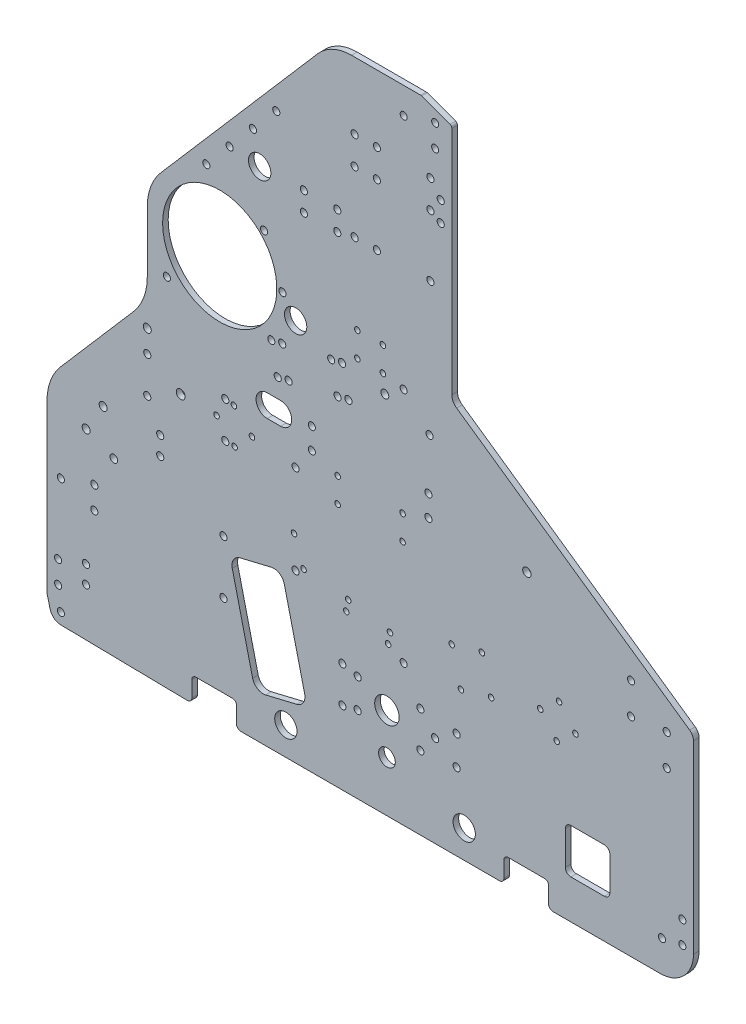
SolidWorks part; units mm, degrees
ref_plane "Front Plane" through (0, 0, 0) normal (0, 0, 1) x (1, 0, 0)
ref_plane "Top Plane" through (0, 0, 0) normal (0, 1, 0) x (1, 0, 0)
ref_plane "Right Plane" through (0, 0, 0) normal (1, 0, 0) x (0, 0, -1)
sketch "Sketch1" plane through (0, 0, 0) normal (0, 0, 1) x (1, 0, 0)
  line L0 (82.55, -20.32) -> (82.55, -6.35)
  line L2 (0, 0) -> (0, 157.48)
  line L4 (368.3, -20.32) -> (368.3, 106.68)
  line L5 (82.55, -6.35) -> (107.95, -6.35)
  line L6 (107.95, -6.35) -> (107.95, -20.32)
  line L7 (107.95, -20.32) -> (260.35, -20.32)
  line L8 (260.35, -20.32) -> (260.35, -6.35)
  line L9 (260.35, -6.35) -> (285.75, -6.35)
  line L10 (285.75, -6.35) -> (285.75, -20.32)
  line L11 (285.75, -20.32) -> (368.3, -20.32)
  line L12 (361.95, 12.7) -> (368.3, 12.7) construction
  line L13 (0, 0) -> (6.35, 0) construction
  line L14 (0.1896, -7.8901) -> (1.7771, -14.2401)
  line L15 (7.8295, -19.0491) -> (82.55, -20.32)
  line L16 (0, 0) -> (0, -6.35)
  line L17 (76.2, 128.905) -> (79.375, 128.905) construction
  line L18 (57.15, 118.5863) -> (101.6, 118.5862) construction
  line L19 (57.15, 118.5863) -> (57.15, 139.2238) construction
  line L20 (101.6, 118.5862) -> (101.6, 139.2237) construction
  line L21 (57.15, 139.2238) -> (101.6, 139.2237) construction
  line L22 (57.15, 118.5863) -> (101.6, 139.2237) construction
  line L23 (101.6, 118.5862) -> (57.15, 139.2238) construction
  line L24 (101.6, 139.2237) -> (125.4682, 147.9111) construction
  line L25 (203.2, 59.805) -> (203.2, 194.805) construction
  line L26 (203.2, 194.805) -> (203.2, 329.805) construction
  line L27 (355.6, 332.105) -> (330.2, 332.105) construction
  line L28 (330.2, 332.105) -> (330.2, 217.805) construction
  line L29 (330.2, 217.805) -> (355.6, 217.805) construction
  line L30 (355.6, 217.805) -> (355.6, 332.105) construction
  line L31 (203.2, 344.805) -> (203.2, 194.805) construction
  line L32 (50.8, 332.105) -> (76.2, 332.105) construction
  line L33 (76.2, 332.105) -> (76.2, 217.805) construction
  line L34 (50.8, 217.805) -> (50.8, 332.105) construction
  line L35 (76.2, 217.805) -> (50.8, 217.805) construction
  line L36 (213.2, 344.805) -> (230.6638, 338.455)
  line L37 (203.2, 344.805) -> (161.925, 344.805)
  line L38 (203.2, 344.805) -> (213.2, 344.805)
  line L39 (348.5362, 344.805) -> (413.4623, 344.805)
  line L40 (348.5362, 344.805) -> (230.6638, 344.805) construction
  line L42 (161.925, 344.805) -> (0, 157.48)
  line L44 (230.6638, 338.455) -> (230.6638, 202.565)
  line L45 (230.6638, 202.565) -> (368.3, 106.68)
  line L46 (213.2, 344.805) -> (-141.0713, 344.805) construction
  line L47 (350.3395, -2.3595) -> (368.3, -20.32) construction
  line L48 (125.4682, 147.9111) -> (133.0882, 147.9111) construction
  line L49 (125.4682, 154.2611) -> (133.0882, 154.2611)
  line L50 (125.4682, 141.5611) -> (133.0882, 141.5611)
  circle A0 centre (6.35, 0) radius 2.032
  circle A1 centre (6.35, 12.7) radius 2.032
  circle A2 centre (361.95, 0) radius 2.032
  circle A3 centre (361.95, 12.7) radius 2.032
  arc A5 (1.7771, -14.2401) -> (7.8295, -19.0491) centre (7.9375, -12.7) ccw
  circle A6 centre (7.9375, -12.7) radius 2.032
  arc A7 (0, -6.35) -> (0.1896, -7.8901) centre (6.35, -6.35) ccw
  circle A8 centre (38.1, 78.105) radius 2.032
  circle A9 centre (76.2, 128.905) radius 2.54
  circle A10 centre (101.6, 118.5862) radius 2.032
  circle A11 centre (101.6, 139.2237) radius 2.032
  circle A12 centre (57.15, 139.2238) radius 2.032
  circle A13 centre (57.15, 118.5863) radius 2.032
  circle A15 centre (203.2, 59.805) radius 2
  circle A16 centre (203.2, 194.805) radius 2
  circle A17 centre (203.2, 329.805) radius 2
  circle A18 centre (63.5, 313.055) radius 2.032
  circle A20 centre (355.6, 332.105) radius 2.032
  circle A21 centre (330.2, 332.105) radius 2.032
  circle A22 centre (355.6, 217.805) radius 2.032
  circle A23 centre (330.2, 217.805) radius 2.032
  circle A24 centre (50.8, 332.105) radius 2.032
  circle A25 centre (76.2, 332.105) radius 2.032
  circle A26 centre (50.8, 217.805) radius 2.032
  circle A27 centre (76.2, 217.805) radius 2.032
  circle A28 centre (221.1381, 335.28) radius 2
  circle A29 centre (224.3138, 298.831) radius 2.032
  circle A30 centre (353.06, 100.7351) radius 2.032
  circle A31 centre (332.74, 115.9751) radius 2.032
  circle A32 centre (332.74, 98.1951) radius 2.032
  circle A33 centre (353.06, 82.9551) radius 2.032
  circle A34 centre (117.3562, 280.4276) radius 2.032
  circle A35 centre (104.0678, 265.0548) radius 2.032
  circle A36 centre (90.7795, 249.682) radius 2.032
  circle A38 centre (130.6445, 295.8004) radius 2.032
  circle A39 centre (68.326, 182.9237) radius 2.032
  circle A40 centre (224.3138, 287.401) radius 2.032
  circle A41 centre (125.4682, 147.9111) radius 6.35
  circle A42 centre (221.1381, 322.58) radius 2
  circle A43 centre (350.3395, -2.3595) radius 2.032
  arc A44 (125.4682, 154.2611) -> (125.4682, 141.5611) centre (125.4682, 147.9111) ccw
  arc A45 (133.0882, 141.5611) -> (133.0882, 154.2611) centre (133.0882, 147.9111) ccw
  point P82 (203.2, 344.805)
  point P90 (368.3, 62.484)
  point P107 (129.2782, 147.9111)
  dimension "D6" = 4.064
  dimension "D10" = 6.35
  dimension "D11" = 4.064
  dimension "D17" = 38.1
  dimension "D27" = 4
  dimension "D31" = 4.064
  dimension "D32" = 41.275
  dimension "D36" = 4.064
  dimension "D47" = 39.624
  dimension "D48" = 4.064
  dimension "D25" = 5.08
  dimension "D26" = 4.064
  dimension "D52" = 4.064
  dimension "D65" = 4.064
  dimension "D69" = 4.064
  dimension "D72" = 12.7
  dimension "D77" = 6.35
  dimension "D2" = 127
  dimension "D3" = 13.97
  dimension "D4" = 25.4
  dimension "D5" = 152.4
  dimension "D7" = 12.7
  dimension "D8" = 6.35
  dimension "D9" = 20.32
  dimension "D12" = 12.7
  dimension "D13" = 1.5875
  dimension "D14" = 82.55
  dimension "D15" = 368.3
  dimension "D16" = 6.35
  dimension "D18" = 98.425
  dimension "D19" = 38.1
  dimension "D20" = 50.8
  dimension "D21" = 3.175
  dimension "D22" = 270
  dimension "D23" = 20.6375
  dimension "D24" = 44.45
  dimension "D28" = 135
  dimension "D29" = 12.7
  dimension "D30" = 15
  dimension "D33" = 63.5
  dimension "D34" = 27.4638
  dimension "D35" = 12.7
  dimension "D37" = 114.3
  dimension "D38" = 25.4
  dimension "D39" = 12.7
  dimension "D40" = 157.48
  dimension "D41" = 142.24
  dimension "D42" = 365.125
  dimension "D43" = 10
  dimension "D44" = 6.35
  dimension "D45" = 31.75
  dimension "D46" = 3.175
  dimension "D49" = 6.35
  dimension "D50" = 203.2
  dimension "D51" = 15.24
  dimension "D53" = 17.78
  dimension "D54" = 17.78
  dimension "D55" = 20.32
  dimension "D56" = 15.24
  dimension "D57" = 92.202
  dimension "D58" = 8.382
  dimension "D59" = 20.32
  dimension "D60" = 20.32
  dimension "D61" = 8.382
  dimension "D62" = 20.32
  dimension "D63" = 8.382
  dimension "D64" = 8.382
  dimension "D66" = 35.052
  dimension "D67" = 68.326
  dimension "D68" = 11.43
  dimension "D70" = 25.4
  dimension "D71" = 110
  dimension "D73" = 17.9381
  dimension "D74" = 12.7
  dimension "D75" = 45
  dimension "D76" = 25.4
  dimension "D79" = 7.62
extrude "Boss-Extrude1" add sketch "Sketch1" along normal blind 3.175 contours L16 A7 L14 A5 L15 L2 A0 A1 A6 region at (171.4194, 119.4541, 0)
fillet "Fillet1" radius 2.286 4 edges at (285.75, -6.35, 1.5875) (107.95, -6.35, 1.5875) (260.35, -6.35, 1.5875) (82.55, -6.35, 1.5875)
fillet "Fillet2" radius 6.35 1 edges at (230.6638, 202.565, 1.5875)
sketch "Sketch2" plane through (0, 0, 0) normal (0, 0, -1) x (-1, 0, 0)
  circle A0 centre (-100.5528, 71.086) radius 2.032 construction
  circle A1 centre (-100.5528, 40.606) radius 2.032 construction
  circle A2 centre (-22.225, 18.2025) radius 2.032 construction
  circle A3 centre (-22.225, 8.0425) radius 2.032 construction
  circle A4 centre (-100.5528, 71.086) radius 2.032
  circle A5 centre (-100.5528, 40.606) radius 2.032
  circle A6 centre (-22.225, 18.2025) radius 2.032
  circle A7 centre (-22.225, 8.0425) radius 2.032
extrude "Cut-Extrude1" cut sketch "Sketch2" against normal through all
fillet "Fillet3" radius 1.5875 2 edges at (230.6638, 338.455, 1.5875) (213.2, 344.805, 1.5875)
sketch "Sketch3" plane through (0, 0, 3.175) normal (0, 0, 1) x (1, 0, 0)
  line L0 (132.9524, 63.2646) -> (132.7215, 64.2281) construction
  line L1 (128.3814, 66.8897) -> (110.6828, 62.6472) construction
  line L2 (114.5132, 58.4237) -> (126.8822, 61.3887) construction
  line L3 (108.0212, 58.3071) -> (108.2522, 57.3436) construction
  line L4 (131.2006, 57.703) -> (140.0164, 20.9265) construction
  line L5 (144.0993, 16.7636) -> (132.9524, 63.2646) construction
  line L6 (108.2522, 57.3436) -> (119.3991, 10.8426) construction
  line L7 (121.1509, 16.4042) -> (112.3351, 53.1807) construction
  line L8 (119.3991, 10.8426) -> (119.6301, 9.8791) construction
  line L9 (144.3303, 15.8001) -> (144.0993, 16.7636) construction
  line L10 (137.8383, 15.6835) -> (125.4694, 12.7185) construction
  line L11 (123.9701, 7.2175) -> (141.6687, 11.4601) construction
  line L12 (132.9524, 63.2646) -> (132.7215, 64.2281)
  line L13 (128.3814, 66.8897) -> (110.6828, 62.6472)
  line L14 (114.5132, 58.4237) -> (126.8822, 61.3887)
  line L15 (108.0212, 58.3071) -> (108.2522, 57.3436)
  line L16 (131.2006, 57.703) -> (140.0164, 20.9265)
  line L17 (144.0993, 16.7636) -> (132.9524, 63.2646)
  line L18 (108.2522, 57.3436) -> (119.3991, 10.8426)
  line L19 (121.1509, 16.4042) -> (112.3351, 53.1807)
  line L20 (119.3991, 10.8426) -> (119.6301, 9.8791)
  line L21 (144.3303, 15.8001) -> (144.0993, 16.7636)
  line L22 (137.8383, 15.6835) -> (125.4694, 12.7185)
  line L23 (123.9701, 7.2175) -> (141.6687, 11.4601)
  line L24 (127.7894, 69.3598) -> (110.0908, 65.1172)
  line L25 (105.5512, 57.715) -> (105.7822, 56.7515)
  line L26 (105.7822, 56.7515) -> (116.9291, 10.2505)
  line L27 (116.9291, 10.2505) -> (117.16, 9.287)
  line L28 (124.5622, 4.7475) -> (142.2608, 8.99)
  line L29 (146.8003, 16.3922) -> (146.5694, 17.3557)
  line L30 (146.5694, 17.3557) -> (135.4225, 63.8567)
  line L31 (135.4225, 63.8567) -> (135.1915, 64.8202)
  line L32 (14.605, -0.1369) -> (103.7278, 32.3011) construction
  line L33 (14.605, -0.1369) -> (103.7278, 32.3011)
  line L34 (0, -6.35) -> (0, 157.48) construction
  line L35 (-39.6666, 74.7152) -> (103.7278, 126.9065) construction
  line L36 (26.9875, 46.9531) -> (26.9875, 59.6531) construction
  line L37 (107.95, -20.32) -> (260.35, -20.32) construction
  line L38 (64.5259, 92.5258) -> (64.5259, 102.9405) construction
  line L39 (131.6538, 14.201) -> (136.0946, -4.3242) construction
  line L40 (136.0946, -4.3242) -> (237.6946, -4.3242) construction
  arc A0 (132.7215, 64.2281) -> (128.6308, 66.9403) centre (129.2206, 63.3889) ccw construction
  arc A1 (110.6828, 62.6472) -> (110.4377, 62.5791) centre (111.522, 59.1463) ccw construction
  arc A2 (128.6308, 66.9403) -> (128.3814, 66.8897) centre (129.2206, 63.3889) ccw construction
  arc A3 (110.4377, 62.5791) -> (108.0212, 58.3071) centre (111.522, 59.1463) ccw construction
  arc A4 (119.6301, 9.8791) -> (123.7207, 7.1669) centre (123.1309, 10.7183) ccw construction
  arc A5 (141.9139, 11.5281) -> (144.3303, 15.8001) centre (140.8295, 14.9609) ccw construction
  arc A6 (141.6687, 11.4601) -> (141.9139, 11.5281) centre (140.8295, 14.9609) ccw construction
  arc A7 (123.7207, 7.1669) -> (123.9701, 7.2175) centre (123.1309, 10.7183) ccw construction
  arc A8 (132.7215, 64.2281) -> (128.6308, 66.9403) centre (129.2206, 63.3889) ccw
  arc A9 (110.6828, 62.6472) -> (110.4377, 62.5791) centre (111.522, 59.1463) ccw
  arc A10 (128.6308, 66.9403) -> (128.3814, 66.8897) centre (129.2206, 63.3889) ccw
  arc A11 (110.4377, 62.5791) -> (108.0212, 58.3071) centre (111.522, 59.1463) ccw
  arc A12 (119.6301, 9.8791) -> (123.7207, 7.1669) centre (123.1309, 10.7183) ccw
  arc A13 (141.9139, 11.5281) -> (144.3303, 15.8001) centre (140.8295, 14.9609) ccw
  arc A14 (141.6687, 11.4601) -> (141.9139, 11.5281) centre (140.8295, 14.9609) ccw
  arc A15 (123.7207, 7.1669) -> (123.9701, 7.2175) centre (123.1309, 10.7183) ccw
  arc A16 (110.0908, 65.1172) -> (109.6726, 65.0012) centre (111.522, 59.1463) ccw
  arc A17 (109.6726, 65.0012) -> (105.5512, 57.715) centre (111.522, 59.1463) ccw
  arc A18 (117.16, 9.287) -> (124.1369, 4.6613) centre (123.1309, 10.7183) ccw
  arc A19 (124.1369, 4.6613) -> (124.5622, 4.7475) centre (123.1309, 10.7183) ccw
  arc A20 (142.2608, 8.99) -> (142.6789, 9.1061) centre (140.8295, 14.9609) ccw
  arc A21 (142.6789, 9.1061) -> (146.8003, 16.3922) centre (140.8295, 14.9609) ccw
  arc A22 (135.1915, 64.8202) -> (128.2147, 69.446) centre (129.2206, 63.3889) ccw
  arc A23 (128.2147, 69.446) -> (127.7894, 69.3598) centre (129.2206, 63.3889) ccw
  circle A24 centre (136.0946, -4.3242) radius 6.35
  circle A25 centre (237.6946, -4.3242) radius 6.35
  circle A26 centre (134.1438, 208.2281) radius 2.032 construction
  circle A33 centre (26.9875, 46.9531) radius 2.032
  circle A34 centre (26.9875, 59.6531) radius 2.032
  circle A35 centre (7.9375, 53.3031) radius 2.032
  circle A37 centre (32.0306, 100.8109) radius 32.385 construction
  circle A38 centre (32.0306, 100.8109) radius 2.286
  circle A39 centre (123.682, 233.4851) radius 2.032 construction
  circle A40 centre (64.5259, 102.9405) radius 2.032
  circle A41 centre (64.5259, 92.5258) radius 2.032
  circle A42 centre (134.1438, 208.2281) radius 2.032
  circle A43 centre (123.682, 233.4851) radius 2.032
  ellipse E0 centre (124.5974, 48.8487) end of major axis (128.5376, 61.3578) minor radius 6 (131.2006, 57.703) -> (126.8822, 61.3887) ccw construction
  ellipse E1 centre (122.2349, 48.2824) end of major axis (113.0518, 57.6456) minor radius 6 (114.5132, 58.4237) -> (112.3351, 53.1807) ccw construction
  ellipse E2 centre (127.7541, 25.2585) end of major axis (131.6942, 37.7675) minor radius 6 (121.1509, 16.4042) -> (125.4694, 12.7185) ccw construction
  ellipse E3 centre (130.1166, 25.8248) end of major axis (139.2998, 16.4616) minor radius 6 (137.8383, 15.6835) -> (140.0164, 20.9265) ccw construction
  ellipse E4 centre (124.5974, 48.8487) end of major axis (128.5376, 61.3578) minor radius 6 (131.2006, 57.703) -> (126.8822, 61.3887) ccw
  ellipse E5 centre (122.2349, 48.2824) end of major axis (131.4181, 38.9192) minor radius 6 (114.5132, 58.4237) -> (112.3351, 53.1807) ccw
  ellipse E6 centre (127.7541, 25.2585) end of major axis (123.8139, 12.7495) minor radius 6 (121.1509, 16.4042) -> (125.4694, 12.7185) ccw
  ellipse E7 centre (130.1166, 25.8248) end of major axis (139.2998, 16.4616) minor radius 6 (137.8383, 15.6835) -> (140.0164, 20.9265) ccw
  point P93 (26.9875, 53.3031)
  point P115 (32.0306, 100.8109)
  dimension "D3" = 64.77
  dimension "D4" = 4.572
  dimension "D8" = 4.064
  dimension "D13" = 12.7
  dimension "D15" = 101.6
  dimension "D2" = 88.9
  dimension "D5" = 7.9375
  dimension "D6" = 19.05
  dimension "D7" = 73.6231
  dimension "D9" = 12.7
  dimension "D10" = 10.4147
  dimension "D11" = 37.5384
  dimension "D12" = 45.5727
  dimension "D14" = 19.05
  dimension "D1" = 2.54
extrude "Cut-Extrude2" cut sketch "Sketch3" against normal through all contours A22 A23 L24 A16 A17 L25 L26 L27 A18 A19 L28 A20 A21 L29 L30 L31 A15 A12 L20 L18 L15 A11 A9 L13 A10 A8 L12 L17 L21 A13 A14 L23 | A12 A15 L23 A14 A13 L21 L17 L12 A8 A10 L13 A9 A11 L15 L18 L20 E7 L22 E6 L19 E5 L14 E4 L16 | L22 E7 L16 E4 L14 E5 L19 E6 | A38 | A41 | A40 | A35 | A34 | A33 | A43 | A42 | A24 | A25 region at (137.844, 39.8506, 3.175) region at (126.1758, 37.0536, 3.175) region at (128.1544, 68.6507, 3.175) region at (32.0306, 100.8109, 3.175) region at (64.5259, 102.9405, 3.175) region at (64.5259, 92.5258, 3.175)
sketch "Sketch4" plane through (0, 0, 3.175) normal (0, 0, 1) x (1, 0, 0)
  line L0 (57.15, 139.2238) -> (101.6, 139.2237) construction
  line L1 (168.275, 21.4312) -> (212.725, 21.4312) construction
  line L2 (168.275, 21.4312) -> (168.275, 42.0687) construction
  line L3 (168.275, 42.0687) -> (212.725, 42.0687) construction
  line L4 (212.725, 21.4312) -> (212.725, 42.0687) construction
  line L5 (168.275, 21.4312) -> (212.725, 42.0687) construction
  line L6 (168.275, 42.0687) -> (212.725, 21.4312) construction
  line L7 (57.15, 118.5863) -> (57.15, 139.2238) construction
  line L8 (107.95, -20.32) -> (260.35, -20.32) construction
  line L9 (193.675, 31.75) -> (177.005, 31.75) construction
  line L10 (190.5, 31.75) -> (193.675, 31.75) construction
  line L11 (6.35, 12.7) -> (361.95, 12.7) construction
  line L12 (107.95, -6.35) -> (107.95, -20.32) construction
  line L13 (193.675, 31.75) -> (220.6625, 31.75) construction
  line L14 (177.005, 23.4569) -> (177.005, 40.0431) construction
  line L15 (213.2, 44.805) -> (193.2, 44.805) construction
  line L16 (213.2, 44.805) -> (213.2, 344.805) construction
  line L17 (213.2, 344.805) -> (193.2, 344.805) construction
  line L18 (193.2, 44.805) -> (193.2, 344.805) construction
  line L19 (213.2, 44.805) -> (193.2, 344.805) construction
  line L20 (213.2, 344.805) -> (193.2, 44.805) construction
  line L21 (226.1381, 335.28) -> (226.1381, 31.75) construction
  line L22 (237.33, 40.0431) -> (233.3612, 40.0431) construction
  line L23 (237.33, 23.4569) -> (233.3612, 23.4569) construction
  circle A0 centre (168.275, 42.0687) radius 2.032
  circle A1 centre (212.725, 42.0687) radius 2.032
  circle A2 centre (212.725, 21.4312) radius 2.032
  circle A3 centre (168.275, 21.4312) radius 2.032
  circle A4 centre (193.675, 31.75) radius 6.985
  circle A7 centre (220.6625, 31.75) radius 14.2875 construction
  circle A8 centre (193.675, 31.75) radius 12.7 construction
  circle A9 centre (177.005, 40.0431) radius 2.032
  circle A10 centre (177.005, 23.4569) radius 2.032
  circle A11 centre (237.33, 40.0431) radius 2.032 construction
  circle A12 centre (237.33, 23.4569) radius 2.032 construction
  circle A13 centre (193.675, 8.4667) radius 4.7625
  circle A14 centre (221.1381, 31.75) radius 2.032
  circle A15 centre (221.1381, 31.75) radius 5 construction
  circle A16 centre (221.1381, 335.28) radius 5 construction
  circle A17 centre (233.3612, 23.4569) radius 2.032
  circle A18 centre (233.3612, 40.0431) radius 2.032
  point P0 (190.5, 31.75)
  point P26 (203.2, 194.805)
  point P38 (177.005, 31.75)
  dimension "D1" = 4.064
  dimension "D4" = 13.97
  dimension "D7" = 9.525
  dimension "D10" = 25.4
  dimension "D11" = 28.575
  dimension "D16" = 10
  dimension "D17" = 4.064
  dimension "D18" = 10
  dimension "D2" = 52.07
  dimension "D3" = 3.175
  dimension "D5" = 82.55
  dimension "D6" = 26.9875
  dimension "D8" = 20
  dimension "D9" = 300
  dimension "D12" = 16.67
  dimension "D13" = 16.5862
  dimension "D14" = 60.325
  dimension "D15" = 23.2833
  dimension "D19" = 3.9688
extrude "Cut-Extrude3" cut sketch "Sketch4" against normal through all
sketch "Sketch5" plane through (0, 0, 0) normal (0, 0, -1) x (-1, 0, 0)
  line L0 (-57.15, 223.5947) -> (-57.15, 165.3337)
  line L1 (-161.925, 344.805) -> (-52.7201, 218.4699) construction
  line L2 (-57.15, 165.3337) -> (0, 99.219)
  line L3 (0, -6.35) -> (0, 157.48) construction
  line L4 (-147.864, -30.311) -> (-147.864, -16.0874)
  line L5 (-50.4199, 215.8089) -> (0, 157.48) construction
  line L6 (-57.15, 223.5947) -> (0, 157.48)
  line L7 (0, 157.48) -> (0, 99.219)
  line L8 (-98.425, 208.2281) -> (-141.6756, 197.9719) construction
  line L9 (-368.3, -20.32) -> (-368.3, 106.68) construction
  line L10 (-285.75, -20.32) -> (-368.3, -20.32) construction
  circle A0 centre (-98.425, 208.2281) radius 32.5437
  circle A1 centre (-141.6756, 197.9719) radius 6.35
  circle A3 centre (-273.4056, 139.7279) radius 2.39
  dimension "D3" = 65.0875
  dimension "D7" = 12.7
  dimension "D8" = 4.78
  dimension "D1" = 38.1
  dimension "D2" = 57.15
  dimension "D4" = 41.275
  dimension "D5" = 41.275
  dimension "D6" = 94.8944
  dimension "D9" = 22.2382
  dimension "D10" = 160.0479
  dimension "D11" = 11.6447
  dimension "D14" = 62.5
  dimension "D13" = 44.45
extrude "Cut-Extrude5" cut sketch "Sketch5" against normal through all contours A0 | L7 L6 L0 L2 | A3 | A1 region at (28.575, 161.4068, 0) region at (98.425, 208.2281, 0) region at (273.4056, 139.7279, 0)
fillet "Fillet4" radius 31.75 3 edges at (0, 99.219, 1.5875) (57.15, 165.3337, 1.5875) (57.15, 223.5947, 1.5875)
sketch "Sketch6" plane through (0, 0, 3.175) normal (0, 0, 1) x (1, 0, 0)
  line L0 (285.75, -20.32) -> (368.3, -20.32) construction
  line L1 (298.45, 27.305) -> (317.5, 27.305)
  line L2 (295.275, 24.13) -> (295.275, 5.08)
  line L3 (298.45, 1.905) -> (317.5, 1.905)
  line L4 (320.675, 24.13) -> (320.675, 5.08)
  line L5 (295.275, 27.305) -> (320.675, 1.905) construction
  line L6 (295.275, 1.905) -> (320.675, 27.305) construction
  line L7 (368.3, -20.32) -> (368.3, 106.68) construction
  arc A0 (295.275, 5.08) -> (298.45, 1.905) centre (298.45, 5.08) ccw
  arc A1 (317.5, 1.905) -> (320.675, 5.08) centre (317.5, 5.08) ccw
  arc A2 (317.5, 27.305) -> (320.675, 24.13) centre (317.5, 24.13) cw
  arc A3 (298.45, 27.305) -> (295.275, 24.13) centre (298.45, 24.13) ccw
  point P0 (307.975, 14.605)
  dimension "D2" = 3.175
  dimension "D1" = 25.4
  dimension "D3" = 22.225
  dimension "D4" = 47.625
extrude "Cut-Extrude6" cut sketch "Sketch6" against normal through all
fillet "Fillet5" radius 25.4 1 edges at (161.925, 344.805, 1.5875)
sketch "Sketch8" plane through (0, 0, 0) normal (0, 0, -1) x (-1, 0, 0)
  line L0 (-230.6638, 337.343) -> (-230.6638, 205.8802) construction
  line L1 (-230.6638, 255.905) -> (-175.26, 255.905) construction
  line L2 (-175.26, 255.905) -> (-175.26, 306.705) construction
  line L3 (-175.26, 306.705) -> (-230.6638, 306.705) construction
  line L4 (-173.5432, 344.805) -> (-212.9203, 344.805) construction
  line L7 (-107.95, -20.32) -> (-260.35, -20.32) construction
  circle A0 centre (-218.44, 290.83) radius 3.9687
  circle A1 centre (-218.44, 290.83) radius 2.032
  circle A2 centre (218.44, 265.7972) radius 3.9687
  circle A3 centre (218.44, 265.7972) radius 2.032
  circle A4 centre (-205.74, 290.83) radius 3.9687
  circle A5 centre (-205.74, 290.83) radius 2.032
  circle A6 centre (-187.96, 290.83) radius 3.9687
  circle A7 centre (-187.96, 290.83) radius 2.032
  circle A8 centre (-187.96, 306.705) radius 2.032
  circle A9 centre (-175.26, 290.83) radius 3.9687
  circle A10 centre (-175.26, 290.83) radius 2.032
  circle A11 centre (-205.74, 306.705) radius 2.032
  circle A13 centre (-205.74, 255.905) radius 2.032
  circle A14 centre (-187.96, 255.905) radius 2.032
  circle A16 centre (-218.44, 306.705) radius 2.032
  circle A17 centre (-175.26, 306.705) radius 2.032
  circle A18 centre (-175.26, 255.905) radius 2.032
  circle A19 centre (-218.44, 255.905) radius 2.032
  circle A20 centre (-218.44, 306.705) radius 3.9687
  circle A21 centre (-205.74, 306.705) radius 3.9687
  circle A22 centre (-175.26, 306.705) radius 3.9687
  circle A23 centre (-218.44, 255.905) radius 3.9687
  circle A24 centre (-205.74, 255.905) radius 3.9687
  circle A25 centre (-187.96, 255.905) radius 3.9687
  circle A26 centre (-175.26, 255.905) radius 3.9687
  circle A27 centre (-187.96, 306.705) radius 3.9687
  dimension "D1" = 7.9375
  dimension "D7" = 4.064
  dimension "D13" = 12.2237
  dimension "D2" = 12.2237
  dimension "D3" = 12.7
  dimension "D4" = 17.78
  dimension "D5" = 12.7
  dimension "D6" = 88.9
  dimension "D8" = 38.1
  dimension "D9" = 17.78
  dimension "D10" = 12.7
  dimension "D11" = 55.4037
  dimension "D12" = 12.7
  dimension "D14" = 311.15
extrude "Cut-Extrude7" cut sketch "Sketch8" against normal through all contours A16 | A17 | A18 | A19 | A8 | A14 | A1 | A7 | A10 region at (218.44, 306.705, 0) region at (175.26, 306.705, 0) region at (175.26, 255.905, 0) region at (218.44, 255.905, 0)
sketch "Sketch10" plane through (0, 0, 3.175) normal (0, 0, 1) x (1, 0, 0)
  circle A4 centre (141.6425, 74.6844) radius 2.032 construction
  circle A5 centre (141.6425, 125.4844) radius 2.032 construction
  circle A6 centre (141.6425, 74.6844) radius 2.032
  circle A7 centre (141.6425, 125.4844) radius 2.032
extrude "Cut-Extrude8" cut sketch "Sketch10" against normal through all
sketch "Sketch11" plane through (0, 0, 3.175) normal (0, 0, 1) x (1, 0, 0)
  ellipse E4 centre (150.8814, 138.43) end of major axis (150.8814, 140.462) minor radius 2.032
  ellipse E5 centre (150.8814, 150.495) end of major axis (150.8814, 152.527) minor radius 2.032
  ellipse E6 centre (217.3024, 150.495) end of major axis (217.3024, 152.527) minor radius 2.032
  ellipse E7 centre (217.3024, 138.43) end of major axis (217.3024, 140.462) minor radius 2.032
extrude "Cut-Extrude9" cut sketch "Sketch11" against normal through all
sketch "Sketch12" plane through (0, 0, 0) normal (0, 0, -1) x (-1, 0, 0)
  line L0 (-173.5432, 344.805) -> (-212.9203, 344.805) construction
  circle A0 centre (-165.4175, 264.635) radius 2.032
  circle A1 centre (-203.2, 329.805) radius 2 construction
  circle A2 centre (-165.4175, 253.5225) radius 2.032
  circle A3 centre (-146.3675, 253.5225) radius 2.032
  circle A4 centre (-146.3675, 264.635) radius 2.032
  dimension "D1" = 80.17
  dimension "D2" = 4.064
  dimension "D3" = 37.7825
  dimension "D4" = 11.1125
  dimension "D5" = 19.05
extrude "Cut-Extrude10" cut sketch "Sketch12" against normal through all
sketch "Sketch14" plane through (0, 0, 0) normal (0, 0, -1) x (-1, 0, 0)
  line L0 (-130.6445, 295.8004) -> (-121.1847, 263.6885) construction
  line L1 (-121.1847, 263.6885) -> (-90.7795, 249.682) construction
  line L2 (-154.3272, 336.0154) -> (-64.88, 232.5373) construction
  line L4 (-118.517, 269.4796) -> (-115.3937, 261.0208) construction
  line L5 (-118.517, 269.4796) -> (-126.9758, 266.3562) construction
  line L6 (-126.9758, 266.3562) -> (-123.8524, 257.8974) construction
  line L7 (-115.3937, 261.0208) -> (-123.8524, 257.8974) construction
  line L8 (-118.517, 269.4796) -> (-123.8524, 257.8974) construction
  line L9 (-126.9758, 266.3562) -> (-115.3937, 261.0208) construction
  circle A0 centre (-121.1847, 263.6885) radius 6.376
  dimension "D1" = 22.225
  dimension "D2" = 9.017
extrude "Cut-Extrude11" cut sketch "Sketch14" against normal through all
sketch "Sketch15" plane through (0, 0, 3.175) normal (0, 0, 1) x (1, 0, 0)
  line L0 (38.1, 78.105) -> (35.0376, 98.2034) construction
  line L1 (20.5874, 75.6997) -> (81.7263, 75.6997) construction
  line L2 (57.15, 139.2238) -> (57.15, 151.9238) construction
  line L3 (52.4937, 153.9549) -> (22.3594, 84.8727) construction
  line L4 (56.0505, 156.8833) -> (192.439, 187.1199) construction
  line L5 (52.4937, 153.9549) -> (37.8292, 107.1192) construction
  line L6 (20.5874, 75.6997) -> (38.1, 78.105) construction
  line L7 (35.0376, 98.2034) -> (37.8292, 107.1192) construction
  line L8 (20.5874, 75.6997) -> (22.3594, 84.8727) construction
  line L9 (38.1, 78.105) -> (17.7697, 78.105) construction
  line L10 (17.7697, 78.105) -> (21.6585, 86.5998) construction
  line L11 (21.6585, 86.5998) -> (52.4937, 153.9549) construction
  circle A0 centre (20.5874, 75.6997) radius 2.159 construction
  circle A1 centre (20.5874, 75.6997) radius 2.159 construction
  circle A2 centre (57.15, 139.2238) radius 2.032 construction
  circle A3 centre (57.15, 139.2238) radius 2.032 construction
  circle A4 centre (57.15, 151.9238) radius 2.286
  circle A5 centre (192.439, 187.1199) radius 2.286
  circle A6 centre (57.15, 151.9238) radius 5.08 construction
  circle A7 centre (38.1, 78.105) radius 2.159 construction
  circle A8 centre (38.1, 78.105) radius 2.159
  arc A9 (163.8737, 173.6806) -> (164.5125, 170.7993) centre (165.557, 172.5423) ccw construction
  arc A10 (173.4397, 172.7784) -> (172.801, 175.6597) centre (171.7565, 173.9167) ccw construction
  arc A11 (172.801, 175.6597) -> (173.4397, 172.7784) centre (171.7565, 173.9167) ccw construction
  arc A12 (164.5125, 170.7993) -> (163.8737, 173.6806) centre (165.557, 172.5423) ccw construction
  arc A13 (169.1589, 192.0883) -> (169.7976, 189.2071) centre (168.1143, 190.3453) ccw construction
  arc A14 (169.7976, 189.2071) -> (169.1589, 192.0883) centre (168.1143, 190.3453) ccw construction
  arc A15 (160.2316, 190.1092) -> (160.8704, 187.2279) centre (161.9149, 188.9709) ccw construction
  arc A16 (160.8704, 187.2279) -> (160.2316, 190.1092) centre (161.9149, 188.9709) ccw construction
  arc A17 (129.7766, 166.1214) -> (130.4154, 163.2402) centre (131.4599, 164.9832) ccw construction
  arc A18 (139.3426, 165.2193) -> (138.7039, 168.1005) centre (137.6593, 166.3576) ccw construction
  arc A19 (138.7039, 168.1005) -> (139.3426, 165.2193) centre (137.6593, 166.3576) ccw construction
  arc A20 (130.4154, 163.2402) -> (129.7766, 166.1214) centre (131.4599, 164.9832) ccw construction
  arc A21 (135.7005, 181.6479) -> (135.0617, 184.5292) centre (134.0172, 182.7862) ccw construction
  arc A22 (135.0617, 184.5292) -> (135.7005, 181.6479) centre (134.0172, 182.7862) ccw construction
  arc A23 (126.1345, 182.55) -> (126.7732, 179.6688) centre (127.8177, 181.4118) ccw construction
  arc A24 (126.7732, 179.6688) -> (126.1345, 182.55) centre (127.8177, 181.4118) ccw construction
  arc A25 (163.8737, 173.6806) -> (164.5125, 170.7993) centre (165.557, 172.5423) ccw
  arc A26 (173.4397, 172.7784) -> (172.801, 175.6597) centre (171.7565, 173.9167) ccw
  arc A27 (172.801, 175.6597) -> (173.4397, 172.7784) centre (171.7565, 173.9167) ccw
  arc A28 (164.5125, 170.7993) -> (163.8737, 173.6806) centre (165.557, 172.5423) ccw
  arc A29 (169.1589, 192.0883) -> (169.7976, 189.2071) centre (168.1143, 190.3453) ccw
  arc A30 (169.7976, 189.2071) -> (169.1589, 192.0883) centre (168.1143, 190.3453) ccw
  arc A31 (160.2316, 190.1092) -> (160.8704, 187.2279) centre (161.9149, 188.9709) ccw
  arc A32 (160.8704, 187.2279) -> (160.2316, 190.1092) centre (161.9149, 188.9709) ccw
  arc A33 (129.7766, 166.1214) -> (130.4154, 163.2402) centre (131.4599, 164.9832) ccw
  arc A34 (139.3426, 165.2193) -> (138.7039, 168.1005) centre (137.6593, 166.3576) ccw
  arc A35 (138.7039, 168.1005) -> (139.3426, 165.2193) centre (137.6593, 166.3576) ccw
  arc A36 (130.4154, 163.2402) -> (129.7766, 166.1214) centre (131.4599, 164.9832) ccw
  arc A37 (135.7005, 181.6479) -> (135.0617, 184.5292) centre (134.0172, 182.7862) ccw
  arc A38 (135.0617, 184.5292) -> (135.7005, 181.6479) centre (134.0172, 182.7862) ccw
  arc A39 (126.1345, 182.55) -> (126.7732, 179.6688) centre (127.8177, 181.4118) ccw
  arc A40 (126.7732, 179.6688) -> (126.1345, 182.55) centre (127.8177, 181.4118) ccw
  circle A41 centre (22.3594, 84.8727) radius 2.286 construction
  circle A42 centre (22.3594, 84.8727) radius 2.286
  point P39 (52.4937, 153.9549)
  dimension "D2" = 4.572
  dimension "D6" = 10.16
  dimension "D1" = 12.7
  dimension "D3" = 139.7
  dimension "D4" = 12.5
  dimension "D5" = 74.0778
  dimension "D7" = 49.0778
extrude "Cut-Extrude12" cut sketch "Sketch15" against normal through all
sketch "Sketch16" plane through (0, 0, 3.175) normal (0, 0, 1) x (1, 0, 0)
  circle A0 centre (98.425, 208.2281) radius 34.925 construction
  circle A1 centre (98.425, 208.2281) radius 34.925
  circle A2 centre (98.425, 208.2281) radius 36.195
  dimension "D1" = 1.27
fillet "Fillet7" radius 5.08 1 edges at (368.3, 106.68, 1.5875)
fillet "Fillet8" radius 2.54 4 edges at (82.55, -20.32, 1.5875) (107.95, -20.32, 1.5875) (260.35, -20.32, 1.5875) (285.75, -20.32, 1.5875)
sketch "Sketch17" plane through (0, 0, 3.175) normal (0, 0, 1) x (1, 0, 0)
  line L0 (230.6638, 337.343) -> (230.6638, 205.8802) construction
  line L1 (173.5432, 344.805) -> (212.9203, 344.805) construction
  circle A0 centre (217.9638, 179.705) radius 2.032
  dimension "D1" = 12.7
  dimension "D3" = 4.064
  dimension "D2" = 165.1
extrude "Cut-Extrude13" cut sketch "Sketch17" against normal through all contours A0
fillet "Fillet9" radius 19.05 1 edges at (368.3, -20.32, 1.5875)
sketch "Sketch18" plane through (0, 0, 3.175) normal (0, 0, 1) x (1, 0, 0)
  line L0 (150.8814, 138.43) -> (217.3024, 138.43) construction
  line L1 (184.0919, 138.43) -> (184.0919, 119.38) construction
  line L2 (165.5919, 119.38) -> (202.5919, 119.38) construction
  line L3 (184.0919, 138.43) -> (184.0919, 210.82) construction
  line L4 (176.8148, 210.82) -> (191.369, 210.82) construction
  line L5 (184.0919, 138.43) -> (184.0919, 65.405) construction
  line L6 (194.31, -20.32) -> (194.31, 64.77) construction
  line L7 (244.4169, 65.405) -> (184.0919, 65.405) construction
  line L8 (253.004, 67.7059) -> (235.8298, 63.1041) construction
  line L9 (202.5919, 133.35) -> (165.5919, 133.35) construction
  line L10 (230.5706, 82.7317) -> (247.7448, 87.3335) construction
  line L11 (244.4169, 65.405) -> (239.1577, 85.0326) construction
  line L12 (184.0919, 119.38) -> (143.4519, 119.38) construction
  line L13 (143.4519, 119.38) -> (143.4519, 85.09) construction
  line L14 (146.1667, 77.6312) -> (140.7371, 92.5488) construction
  line L15 (184.0919, 138.43) -> (116.7819, 138.43) construction
  line L16 (116.7819, 138.43) -> (116.7819, 128.27) construction
  line L17 (116.7819, 128.27) -> (106.4905, 138.5614) construction
  line L18 (111.6362, 133.4157) -> (101.7579, 123.5374) construction
  line L19 (184.0919, 138.43) -> (285.6919, 138.43) construction
  line L20 (285.6919, 138.43) -> (285.6919, 70.485) construction
  line L21 (290.3695, 64.9104) -> (281.0143, 76.0596) construction
  line L22 (96.6123, 128.6831) -> (106.9036, 118.3917) construction
  line L23 (184.0919, 210.82) -> (184.0919, 196.85) construction
  line L24 (176.8148, 196.85) -> (191.369, 196.85) construction
  line L25 (285.6919, 70.485) -> (296.3936, 79.4647) construction
  line L26 (291.7159, 85.0393) -> (301.0712, 73.8902) construction
  line L27 (110.49, -20.32) -> (257.81, -20.32) construction
  line L28 (107.95, -8.636) -> (107.95, -17.78) construction
  line L29 (194.31, 64.77) -> (170.511, 68.9664) construction
  line L30 (170.511, 68.9664) -> (171.6137, 75.2199) construction
  line L31 (194.31, 64.77) -> (195.4127, 71.0235) construction
  circle A0 centre (170.511, 68.9664) radius 1.5875
  circle A1 centre (150.8814, 138.43) radius 2.032 construction
  circle A2 centre (217.3024, 138.43) radius 2.032 construction
  circle A3 centre (150.8814, 138.43) radius 2.032
  circle A4 centre (217.3024, 138.43) radius 2.032
  circle A5 centre (165.5919, 119.38) radius 1.5875
  circle A6 centre (202.5919, 119.38) radius 1.5875
  circle A7 centre (176.8148, 210.82) radius 1.5875
  circle A8 centre (191.369, 210.82) radius 1.5875
  circle A9 centre (165.5919, 133.35) radius 1.5875
  circle A10 centre (202.5919, 133.35) radius 1.5875
  circle A11 centre (235.8298, 63.1041) radius 1.5875
  circle A12 centre (253.004, 67.7059) radius 1.5875
  circle A13 centre (230.5706, 82.7317) radius 1.5875
  circle A14 centre (247.7448, 87.3335) radius 1.5875
  circle A15 centre (140.7371, 92.5488) radius 1.5875
  circle A16 centre (146.1667, 77.6312) radius 1.5875
  circle A17 centre (116.7819, 128.27) radius 1.5875
  circle A18 centre (106.4905, 138.5614) radius 1.5875
  circle A20 centre (281.0143, 76.0596) radius 1.5875
  circle A21 centre (290.3695, 64.9104) radius 1.5875
  circle A22 centre (96.6123, 128.6831) radius 1.5875
  circle A23 centre (106.9036, 118.3917) radius 1.5875
  circle A24 centre (176.8148, 196.85) radius 1.5875
  circle A25 centre (191.369, 196.85) radius 1.5875
  circle A26 centre (291.7159, 85.0393) radius 1.5875
  circle A27 centre (301.0712, 73.8902) radius 1.5875
  circle A28 centre (194.31, 64.77) radius 1.5875
  circle A29 centre (171.6137, 75.2199) radius 1.5875
  circle A30 centre (195.4127, 71.0235) radius 1.5875
  point P3 (184.0919, 119.38)
  point P17 (184.0919, 210.82)
  point P24 (244.4169, 65.405)
  point P27 (184.0919, 133.35)
  point P41 (143.4519, 85.09)
  point P55 (285.6919, 70.485)
  point P60 (101.7579, 123.5374)
  point P66 (184.0919, 196.85)
  point P72 (296.3936, 79.4647)
  dimension "D3" = 3.175
  dimension "D6" = 73.025
  dimension "D8" = 13.97
  dimension "D11" = 20.32
  dimension "D12" = 40.64
  dimension "D14" = 15.875
  dimension "D18" = 45
  dimension "D23" = 14.5542
  dimension "D20" = 13.97
  dimension "D25" = 13.97
  dimension "D26" = 13.97
  dimension "D29" = 3.175
  dimension "D32" = 6.35
  dimension "D1" = 19.05
  dimension "D2" = 37
  dimension "D4" = 72.39
  dimension "D5" = 14.5542
  dimension "D7" = 60.325
  dimension "D9" = 17.78
  dimension "D10" = 75
  dimension "D13" = 34.29
  dimension "D15" = 20
  dimension "D16" = 67.31
  dimension "D17" = 10.16
  dimension "D19" = 14.5542
  dimension "D21" = 101.6
  dimension "D22" = 67.945
  dimension "D24" = 40
  dimension "D27" = 85.09
  dimension "D28" = 86.36
  dimension "D30" = 24.1661
  dimension "D31" = 100
extrude "Cut-Extrude14" cut sketch "Sketch18" against normal through all contours A6 | A5 | A12 | A11 | A13 | A14 | A10 | A9 | A7 | A8 | A16 | A15 | A18 | A17 | A20 | A21 | A27 | A26 | A23 | A22 | A24 | A25 | A28 | A0 | A29 | A30
equation "\"D7@Sketch15\"=\"D5@Sketch15\"-25mm"
